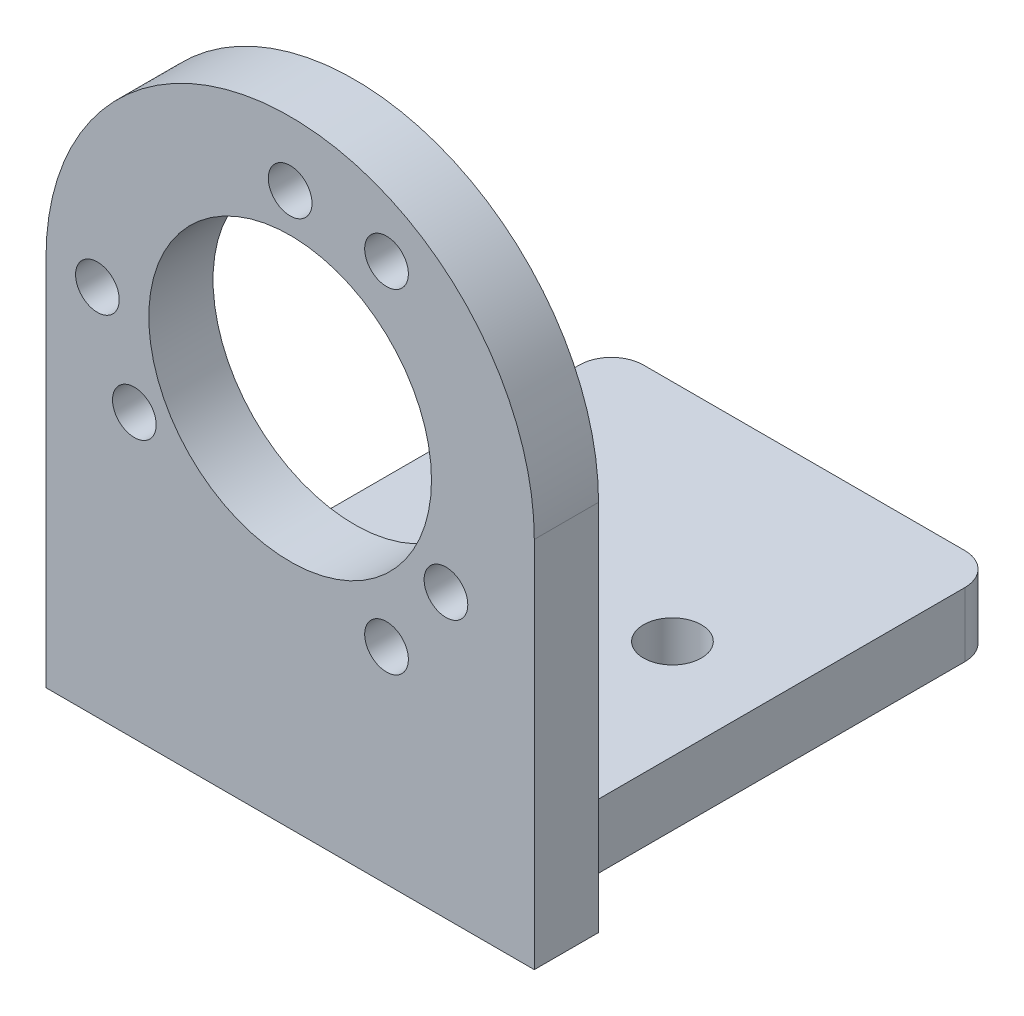
SolidWorks part; units mm, degrees
material "ABS"
ref_plane "Front Plane" through (0, 0, 0) normal (0, 0, 1) x (1, 0, 0)
ref_plane "Top Plane" through (0, 0, 0) normal (0, 1, 0) x (1, 0, 0)
ref_plane "Right Plane" through (0, 0, 0) normal (1, 0, 0) x (0, 0, -1)
sketch "Sketch1" plane through (0, 0, 0) normal (0, 0, 1) x (1, 0, 0)
  line L0 (-19, 0) -> (-19, -29)
  line L1 (-19, -29) -> (19, -29)
  line L2 (19, -29) -> (19, 0)
  circle A0 centre (0, 0) radius 19
  circle A1 centre (0, 0) radius 11
  dimension "D1" = 38
  dimension "D2" = 10
  dimension "D3" = 22
extrude "Boss-Extrude1" add sketch "Sketch1" along normal blind 5 contours A0 A1 | A0 L0 L1 L2 region at (0, -21.3225, 0) region at (0, 18.4626, 0)
sketch "Sketch2" plane through (0, 0, 0) normal (0, 0, -1) x (-1, 0, 0)
  line L1 (-15, -29) -> (15, -29)
  line L2 (-15, -29) -> (-15, -24)
  line L3 (-15, -24) -> (15, -24)
  line L4 (15, -29) -> (15, -24)
  line L5 (19, -29) -> (-19, -29) construction
  point P5 (-9.2855, -23.5403)
  point P8 (0, -24)
  dimension "D1" = 5
  dimension "D2" = 30
extrude "Boss-Extrude2" add sketch "Sketch2" along normal blind 35
hole_wizard "M3 Clearance Hole1" positions "Sketch3" profile "Sketch4" hole size "M3" standard "ANSI Metric" end condition up to next
sketch "Sketch3" plane through (0, 0, 5) normal (0, 0, 1) x (1, 0, 0)
  line L0 (0, 0) -> (0, 14) construction
  line L2 (0, 0) -> (7.5, 12.9904) construction
  circle A0 centre (0, 0) radius 14 construction
  circle A1 centre (0, 0) radius 15 construction
  point P5 (0, 14)
  point P14 (12.1244, -7)
  point P15 (-12.1244, -7)
  point P19 (7.5, 12.9904)
  point P32 (7.5, -12.9904)
  point P33 (-15, 0)
  dimension "D1" = 28
  dimension "D2" = 3
  dimension "D3" = 30
  dimension "D4" = 30
sketch "Sketch4" plane through (-15, 0, 5) normal (1, 0, 0) x (0, -1, 0)
  line L0 (0, 0) -> (0, 5)
  line L1 (0, 5) -> (1.7, 5)
  line L2 (1.7, 5) -> (1.7, 0)
  line L5 (1.7, 0) -> (0, 0)
  line L11 (0, -6.35) -> (0, 107.95) construction
  dimension "Thru Hole Dia." = 3.4
  dimension "Thru Hole Depth" = 5
hole_wizard "M4 Clearance Hole1" positions "Sketch5" profile "Sketch6" hole size "M4" standard "ANSI Metric" end condition up to next
sketch "Sketch5" plane through (0, -24, 0) normal (0, 1, 0) x (1, 0, 0)
  line L0 (7.25, 17.5) -> (-7.25, 17.5) construction
  line L1 (-15, 35) -> (15, 35) construction
  point P1 (-7.25, 17.5)
  point P20 (7.25, 17.5)
  point P24 (0, 17.5)
  dimension "D1" = 14.5
  dimension "D2" = 17.5
sketch "Sketch6" plane through (-7.25, -24, -17.5) normal (1, 0, 0) x (0, 0, 1)
  line L0 (0, 0) -> (0, 5)
  line L1 (0, 5) -> (2.25, 5)
  line L2 (2.25, 5) -> (2.25, 0)
  line L5 (2.25, 0) -> (0, 0)
  line L11 (0, -6.35) -> (0, 107.95) construction
  dimension "Thru Hole Dia." = 4.5
  dimension "Thru Hole Depth" = 5
fillet "Fillet1" radius 2.5 5 edges at (-15, -26.5, -35) (15, -26.5, -35) (0, -24, 0) (-15, -26.5, 0) (15, -26.5, 0)
